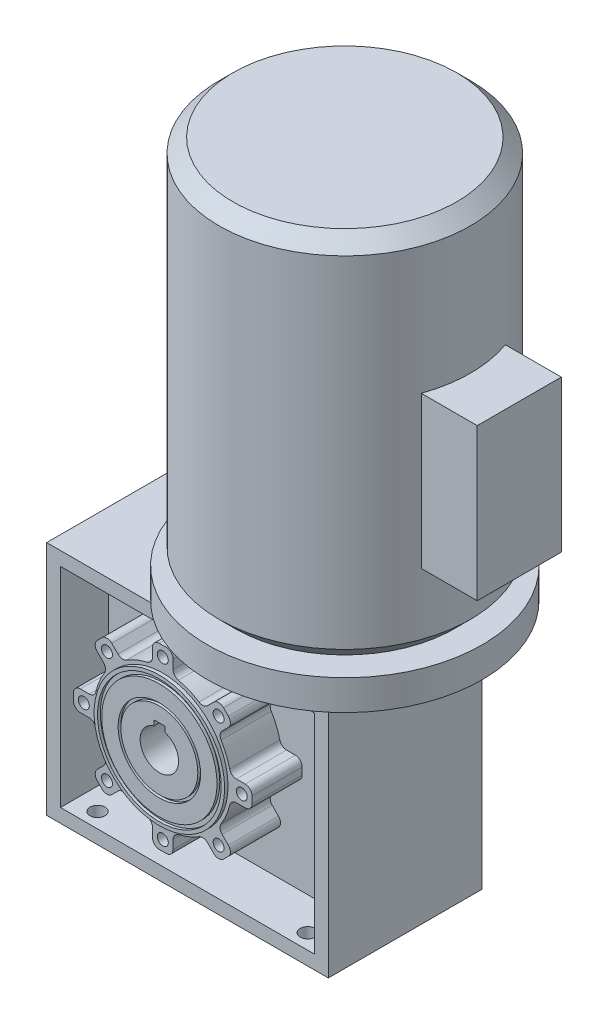
SolidWorks part; units mm, degrees
material "201 Annealed Stainless Steel (SS)"
ref_plane "Front Plane" through (0, 0, 0) normal (0, 0, 1) x (1, 0, 0)
ref_plane "Top Plane" through (0, 0, 0) normal (0, 1, 0) x (1, 0, 0)
ref_plane "Right Plane" through (0, 0, 0) normal (1, 0, 0) x (0, 0, -1)
sketch "Sketch1" plane through (0, 0, 0) normal (0, 0, 1) x (1, 0, 0)
  line L0 (214, -77.2819) -> (214, 49.2287) construction
  line L1 (61, -65.4596) -> (61, 55.7174) construction
  line L2 (125, 99.4164) -> (125, 103.3) construction
  line L3 (125, 103.3) -> (117, 103.3) construction
  line L4 (117, 103.3) -> (117, 99.4164) construction
  line L5 (121, 86) -> (121, 117.4858) construction
  line L8 (35, 0) -> (240, 0)
  line L9 (240, 0) -> (240, 172)
  line L10 (240, 172) -> (35, 172)
  line L11 (35, 172) -> (35, 0)
  circle A1 centre (121, 86) radius 14
  dimension "D1" = 86
  dimension "D2" = 86
  dimension "D6" = 28
  dimension "D3" = 205
  dimension "D4" = 172
  dimension "D5" = 35
  dimension "D7" = 93
  dimension "D8" = 60
  dimension "D9" = 31.3
  dimension "D10" = 8
extrude "Boss-Extrude1" add sketch "Sketch1" against normal blind 112
ref_plane "Plane1" through (0, 0, -56) normal (0, 0, 1) x (1, 0, 0)
sketch "Sketch3" plane through (0, 172, 0) normal (0, 1, 0) x (1, 0, 0)
  circle A1 centre (228, 65) radius 110
sketch "Sketch2" plane through (0, 0, -56) normal (0, 0, 1) x (1, 0, 0)
  line L0 (196, 62.1488) -> (196, 501.4136) construction
  line L1 (275.7058, 210) -> (287.5335, 221.8277)
  line L2 (287.5335, 221.8277) -> (287.5335, 469.9173)
  line L3 (287.5335, 469.9173) -> (277.4507, 480)
  line L4 (277.4507, 480) -> (196, 480)
  line L5 (35, 0) -> (240, 0) construction
  line L6 (275.7058, 210) -> (296, 210)
  line L7 (296, 210) -> (296, 199)
  line L8 (196, 210) -> (275.7058, 210) construction
  line L9 (196, 172) -> (196, 480)
  line L10 (296, 199) -> (237.6683, 199) construction
  line L11 (35, 0) -> (240, 0) construction
  line L12 (237.6683, 188) -> (237.6683, 172)
  line L13 (240, 172) -> (35, 172) construction
  line L14 (237.6683, 172) -> (196, 172)
  line L15 (296, 199) -> (296, 188)
  line L16 (296, 188) -> (237.6683, 188)
  dimension "D1" = 480
  dimension "D2" = 281
  dimension "D3" = 199
  dimension "D4" = 75
  dimension "D5" = 113
  dimension "D6" = 45
  dimension "D7" = 45
  dimension "D8" = 200
  dimension "D9" = 188
revolve "Motor" add sketch "Sketch2" angle 360 about L0
sketch "Sketch4" plane through (0, 0, 0) normal (0, 0, 1) x (1, 0, 0)
  line L8 (230, 10) -> (230, 162)
  line L9 (45, 10) -> (230, 10)
  line L10 (45, 162) -> (45, 10)
  line L11 (230, 162) -> (45, 162)
  line L12 (230, 10) -> (230, 162)
  line L13 (45, 10) -> (230, 10)
  line L14 (45, 162) -> (45, 10)
  line L15 (230, 162) -> (45, 162)
  circle A0 centre (121, 86) radius 50
  circle A1 centre (121, 86) radius 14 construction
  dimension "D2" = 100
  dimension "D1" = 10
extrude "Cut-Extrude1" cut sketch "Sketch4" against normal blind 35
sketch "Sketch5" plane through (0, 0, -112) normal (0, 0, -1) x (-1, 0, 0)
  line L4 (-230, 162) -> (-230, 10)
  line L5 (-45, 162) -> (-230, 162)
  line L6 (-45, 10) -> (-45, 162)
  line L7 (-230, 10) -> (-45, 10)
  line L8 (-230, 162) -> (-230, 10)
  line L9 (-45, 162) -> (-230, 162)
  line L10 (-45, 10) -> (-45, 162)
  line L11 (-230, 10) -> (-45, 10)
  circle A1 centre (-121, 86) radius 50
  circle A2 centre (-121, 86) radius 50
  dimension "D1" = 0
  dimension "D2" = 0
extrude "Cut-Extrude2" cut sketch "Sketch5" against normal blind 46
sketch "Sketch6" plane through (0, 0, 0) normal (0, 0, 1) x (1, 0, 0)
  line L0 (121, 86) -> (121, 219.6781) construction
  line L1 (121, 86) -> (299.9938, 86) construction
  line L2 (113.5, 135.4343) -> (113.5, 151)
  line L3 (113.5, 151) -> (128.5, 151)
  line L4 (128.5, 135.4343) -> (128.5, 151)
  circle A0 centre (121, 143.5) radius 4 construction
  circle A1 centre (121, 28.5) radius 4 construction
  arc A2 (128.5, 135.4343) -> (113.5, 135.4343) centre (121, 86) ccw
  circle A3 centre (121, 86) radius 50 construction
  circle A4 centre (121, 86) radius 57.5 construction
  point P14 (121, 151)
  dimension "D1" = 8
  dimension "D2" = 115
  dimension "D4" = 15
  dimension "D3" = 15
extrude "Boss-Extrude2" add sketch "Sketch6" against normal up to surface (112 mm away) up to face at (135, 86, -112)
ref_axis "Axis1" through (121, 86, -112) along (0, 0, 1)
sketch "Sketch7" plane through (0, 0, 0) normal (0, 0, 1) x (1, 0, 0)
  circle A0 centre (121, 143.5) radius 4 construction
  circle A1 centre (121, 143.5) radius 4
extrude "Cut-Extrude3" cut sketch "Sketch7" against normal through all
fillet "Fillet1" radius 5 8 edges at (128.5, 151, -17.5) (128.5, 135.4343, -17.5) (113.5, 135.4343, -17.5) (113.5, 151, -17.5) (128.5, 135.4343, -89) (128.5, 151, -89) (113.5, 151, -89) (113.5, 135.4343, -89)
pattern_circular "CirPattern1" count 8 over 360 about axis through (121, 86, -112) along (0, 0, 1) of "Boss-Extrude2", "Cut-Extrude3", "Fillet1"
sketch "Sketch8" plane through (0, 0, 0) normal (0, 0, 1) x (1, 0, 0)
  line L4 (88.4302, 129.1764) -> (83.8769, 133.7297)
  line L14 (88.4302, 129.1764) -> (83.8769, 133.7297)
  line L16 (76.8058, 133.7297) -> (73.2703, 130.1942)
  line L18 (76.8058, 133.7297) -> (73.2703, 130.1942)
  line L20 (73.2703, 123.1231) -> (77.8236, 118.5698)
  line L22 (73.2703, 123.1231) -> (77.8236, 118.5698)
  line L76 (67.4393, 93.5) -> (61, 93.5)
  line L78 (67.4393, 93.5) -> (61, 93.5)
  line L80 (56, 88.5) -> (56, 83.5)
  line L82 (56, 88.5) -> (56, 83.5)
  line L84 (61, 78.5) -> (67.4393, 78.5)
  line L86 (61, 78.5) -> (67.4393, 78.5)
  line L88 (77.8236, 53.4302) -> (73.2703, 48.8769)
  line L90 (77.8236, 53.4302) -> (73.2703, 48.8769)
  line L92 (73.2703, 41.8058) -> (76.8058, 38.2703)
  line L94 (73.2703, 41.8058) -> (76.8058, 38.2703)
  line L96 (83.8769, 38.2703) -> (88.4302, 42.8236)
  line L98 (83.8769, 38.2703) -> (88.4302, 42.8236)
  line L100 (113.5, 32.4393) -> (113.5, 26)
  line L101 (113.5, 32.4393) -> (113.5, 26)
  line L102 (118.5, 21) -> (123.5, 21)
  line L103 (118.5, 21) -> (123.5, 21)
  line L104 (128.5, 26) -> (128.5, 32.4393)
  line L105 (128.5, 26) -> (128.5, 32.4393)
  line L106 (153.5698, 42.8236) -> (158.1231, 38.2703)
  line L107 (153.5698, 42.8236) -> (158.1231, 38.2703)
  line L108 (165.1942, 38.2703) -> (168.7297, 41.8058)
  line L109 (165.1942, 38.2703) -> (168.7297, 41.8058)
  line L110 (168.7297, 48.8769) -> (164.1764, 53.4302)
  line L111 (168.7297, 48.8769) -> (164.1764, 53.4302)
  line L112 (174.5607, 78.5) -> (181, 78.5)
  line L113 (174.5607, 78.5) -> (181, 78.5)
  line L114 (186, 83.5) -> (186, 88.5)
  line L115 (186, 83.5) -> (186, 88.5)
  line L116 (181, 93.5) -> (174.5607, 93.5)
  line L117 (181, 93.5) -> (174.5607, 93.5)
  line L118 (164.1764, 118.5698) -> (168.7297, 123.1231)
  line L119 (164.1764, 118.5698) -> (168.7297, 123.1231)
  line L120 (168.7297, 130.1942) -> (165.1942, 133.7297)
  line L121 (168.7297, 130.1942) -> (165.1942, 133.7297)
  line L122 (158.1231, 133.7297) -> (153.5698, 129.1764)
  line L123 (158.1231, 133.7297) -> (153.5698, 129.1764)
  line L124 (128.5, 139.5607) -> (128.5, 146)
  line L125 (128.5, 139.5607) -> (128.5, 146)
  line L126 (123.5, 151) -> (118.5, 151)
  line L127 (123.5, 151) -> (118.5, 151)
  line L128 (113.5, 146) -> (113.5, 139.5607)
  line L129 (113.5, 146) -> (113.5, 139.5607)
  circle A0 centre (161.6586, 45.3414) radius 4 construction
  circle A1 centre (121, 28.5) radius 4 construction
  circle A2 centre (80.3414, 45.3414) radius 4 construction
  circle A3 centre (63.5, 86) radius 4 construction
  circle A4 centre (178.5, 86) radius 4 construction
  circle A5 centre (161.6586, 126.6586) radius 4 construction
  circle A6 centre (121, 86) radius 14 construction
  circle A7 centre (80.3414, 126.6586) radius 4 construction
  circle A24 centre (121, 143.5) radius 4 construction
  circle A25 centre (161.6586, 45.3414) radius 4
  circle A26 centre (121, 28.5) radius 4
  circle A27 centre (80.3414, 45.3414) radius 4
  circle A28 centre (63.5, 86) radius 4
  circle A29 centre (178.5, 86) radius 4
  circle A30 centre (161.6586, 126.6586) radius 4
  circle A31 centre (121, 86) radius 14
  circle A32 centre (80.3414, 126.6586) radius 4
  circle A33 centre (121, 143.5) radius 4
  arc A70 (168.7297, 123.1231) -> (168.7297, 130.1942) centre (165.1942, 126.6586) ccw
  arc A72 (168.7297, 123.1231) -> (168.7297, 130.1942) centre (165.1942, 126.6586) ccw
  arc A74 (165.1942, 133.7297) -> (158.1231, 133.7297) centre (161.6586, 130.1942) ccw
  arc A78 (165.1942, 133.7297) -> (158.1231, 133.7297) centre (161.6586, 130.1942) ccw
  arc A82 (147.3948, 128.4654) -> (153.5698, 129.1764) centre (150.0343, 132.712) ccw
  arc A86 (147.3948, 128.4654) -> (153.5698, 129.1764) centre (150.0343, 132.712) ccw
  arc A90 (147.3948, 128.4654) -> (132.3636, 134.6916) centre (121, 86) ccw
  arc A94 (147.3948, 128.4654) -> (132.3636, 134.6916) centre (121, 86) ccw
  arc A98 (128.5, 139.5607) -> (132.3636, 134.6916) centre (133.5, 139.5607) ccw
  arc A102 (128.5, 139.5607) -> (132.3636, 134.6916) centre (133.5, 139.5607) ccw
  arc A106 (128.5, 146) -> (123.5, 151) centre (123.5, 146) ccw
  arc A110 (128.5, 146) -> (123.5, 151) centre (123.5, 146) ccw
  arc A114 (118.5, 151) -> (113.5, 146) centre (118.5, 146) ccw
  arc A118 (118.5, 151) -> (113.5, 146) centre (118.5, 146) ccw
  arc A122 (109.6364, 134.6916) -> (113.5, 139.5607) centre (108.5, 139.5607) ccw
  arc A126 (109.6364, 134.6916) -> (113.5, 139.5607) centre (108.5, 139.5607) ccw
  arc A130 (109.6364, 134.6916) -> (94.6052, 128.4654) centre (121, 86) ccw
  arc A134 (109.6364, 134.6916) -> (94.6052, 128.4654) centre (121, 86) ccw
  arc A138 (88.4302, 129.1764) -> (94.6052, 128.4654) centre (91.9657, 132.712) ccw
  arc A142 (88.4302, 129.1764) -> (94.6052, 128.4654) centre (91.9657, 132.712) ccw
  arc A146 (83.8769, 133.7297) -> (76.8058, 133.7297) centre (80.3414, 130.1942) ccw
  arc A148 (83.8769, 133.7297) -> (76.8058, 133.7297) centre (80.3414, 130.1942) ccw
  arc A150 (73.2703, 130.1942) -> (73.2703, 123.1231) centre (76.8058, 126.6586) ccw
  arc A152 (73.2703, 130.1942) -> (73.2703, 123.1231) centre (76.8058, 126.6586) ccw
  arc A154 (78.5346, 112.3948) -> (77.8236, 118.5698) centre (74.288, 115.0343) ccw
  arc A156 (78.5346, 112.3948) -> (77.8236, 118.5698) centre (74.288, 115.0343) ccw
  arc A158 (78.5346, 112.3948) -> (72.3084, 97.3636) centre (121, 86) ccw
  arc A160 (78.5346, 112.3948) -> (72.3084, 97.3636) centre (121, 86) ccw
  arc A162 (67.4393, 93.5) -> (72.3084, 97.3636) centre (67.4393, 98.5) ccw
  arc A164 (67.4393, 93.5) -> (72.3084, 97.3636) centre (67.4393, 98.5) ccw
  arc A166 (61, 93.5) -> (56, 88.5) centre (61, 88.5) ccw
  arc A168 (61, 93.5) -> (56, 88.5) centre (61, 88.5) ccw
  arc A170 (56, 83.5) -> (61, 78.5) centre (61, 83.5) ccw
  arc A172 (56, 83.5) -> (61, 78.5) centre (61, 83.5) ccw
  arc A174 (72.3084, 74.6364) -> (67.4393, 78.5) centre (67.4393, 73.5) ccw
  arc A176 (72.3084, 74.6364) -> (67.4393, 78.5) centre (67.4393, 73.5) ccw
  arc A178 (72.3084, 74.6364) -> (78.5346, 59.6052) centre (121, 86) ccw
  arc A180 (72.3084, 74.6364) -> (78.5346, 59.6052) centre (121, 86) ccw
  arc A182 (77.8236, 53.4302) -> (78.5346, 59.6052) centre (74.288, 56.9657) ccw
  arc A184 (77.8236, 53.4302) -> (78.5346, 59.6052) centre (74.288, 56.9657) ccw
  arc A186 (73.2703, 48.8769) -> (73.2703, 41.8058) centre (76.8058, 45.3414) ccw
  arc A187 (73.2703, 48.8769) -> (73.2703, 41.8058) centre (76.8058, 45.3414) ccw
  arc A188 (76.8058, 38.2703) -> (83.8769, 38.2703) centre (80.3414, 41.8058) ccw
  arc A189 (76.8058, 38.2703) -> (83.8769, 38.2703) centre (80.3414, 41.8058) ccw
  arc A190 (94.6052, 43.5346) -> (88.4302, 42.8236) centre (91.9657, 39.288) ccw
  arc A191 (94.6052, 43.5346) -> (88.4302, 42.8236) centre (91.9657, 39.288) ccw
  arc A192 (94.6052, 43.5346) -> (109.6364, 37.3084) centre (121, 86) ccw
  arc A193 (94.6052, 43.5346) -> (109.6364, 37.3084) centre (121, 86) ccw
  arc A194 (113.5, 32.4393) -> (109.6364, 37.3084) centre (108.5, 32.4393) ccw
  arc A195 (113.5, 32.4393) -> (109.6364, 37.3084) centre (108.5, 32.4393) ccw
  arc A196 (113.5, 26) -> (118.5, 21) centre (118.5, 26) ccw
  arc A197 (113.5, 26) -> (118.5, 21) centre (118.5, 26) ccw
  arc A198 (123.5, 21) -> (128.5, 26) centre (123.5, 26) ccw
  arc A199 (123.5, 21) -> (128.5, 26) centre (123.5, 26) ccw
  arc A200 (132.3636, 37.3084) -> (128.5, 32.4393) centre (133.5, 32.4393) ccw
  arc A201 (132.3636, 37.3084) -> (128.5, 32.4393) centre (133.5, 32.4393) ccw
  arc A202 (132.3636, 37.3084) -> (147.3948, 43.5346) centre (121, 86) ccw
  arc A203 (132.3636, 37.3084) -> (147.3948, 43.5346) centre (121, 86) ccw
  arc A204 (153.5698, 42.8236) -> (147.3948, 43.5346) centre (150.0343, 39.288) ccw
  arc A205 (153.5698, 42.8236) -> (147.3948, 43.5346) centre (150.0343, 39.288) ccw
  arc A206 (158.1231, 38.2703) -> (165.1942, 38.2703) centre (161.6586, 41.8058) ccw
  arc A207 (158.1231, 38.2703) -> (165.1942, 38.2703) centre (161.6586, 41.8058) ccw
  arc A208 (168.7297, 41.8058) -> (168.7297, 48.8769) centre (165.1942, 45.3414) ccw
  arc A209 (168.7297, 41.8058) -> (168.7297, 48.8769) centre (165.1942, 45.3414) ccw
  arc A210 (163.4654, 59.6052) -> (164.1764, 53.4302) centre (167.712, 56.9657) ccw
  arc A211 (163.4654, 59.6052) -> (164.1764, 53.4302) centre (167.712, 56.9657) ccw
  arc A212 (163.4654, 59.6052) -> (169.6916, 74.6364) centre (121, 86) ccw
  arc A213 (163.4654, 59.6052) -> (169.6916, 74.6364) centre (121, 86) ccw
  arc A214 (174.5607, 78.5) -> (169.6916, 74.6364) centre (174.5607, 73.5) ccw
  arc A215 (174.5607, 78.5) -> (169.6916, 74.6364) centre (174.5607, 73.5) ccw
  arc A216 (181, 78.5) -> (186, 83.5) centre (181, 83.5) ccw
  arc A217 (181, 78.5) -> (186, 83.5) centre (181, 83.5) ccw
  arc A218 (186, 88.5) -> (181, 93.5) centre (181, 88.5) ccw
  arc A219 (186, 88.5) -> (181, 93.5) centre (181, 88.5) ccw
  arc A220 (169.6916, 97.3636) -> (174.5607, 93.5) centre (174.5607, 98.5) ccw
  arc A221 (169.6916, 97.3636) -> (174.5607, 93.5) centre (174.5607, 98.5) ccw
  arc A222 (169.6916, 97.3636) -> (163.4654, 112.3948) centre (121, 86) ccw
  arc A223 (169.6916, 97.3636) -> (163.4654, 112.3948) centre (121, 86) ccw
  arc A224 (164.1764, 118.5698) -> (163.4654, 112.3948) centre (167.712, 115.0343) ccw
  arc A225 (164.1764, 118.5698) -> (163.4654, 112.3948) centre (167.712, 115.0343) ccw
  dimension "D1" = 0
extrude "Boss-Extrude one side" add sketch "Sketch8" along normal blind 1.5
sketch "Sketch9" plane through (0, 0, 1.5) normal (0, 0, 1) x (1, 0, 0)
  circle A0 centre (121, 86) radius 47.5
  circle A1 centre (121, 86) radius 14 construction
  circle A2 centre (121, 86) radius 14
  dimension "D1" = 95
extrude "Boss-Extrude5" add sketch "Sketch9" along normal blind 2.5
sketch "Sketch10" plane through (0, 0, 4) normal (0, 0, 1) x (1, 0, 0)
  circle A0 centre (121, 86) radius 45
  circle A1 centre (121, 86) radius 42
  dimension "D1" = 90
  dimension "D2" = 84
extrude "Cut-Extrude4" cut sketch "Sketch10" against normal blind 2
sketch "Sketch11" plane through (0, 0, 4) normal (0, 0, 1) x (1, 0, 0)
  circle A0 centre (121, 86) radius 30
  circle A1 centre (121, 86) radius 14 construction
  circle A2 centre (121, 86) radius 28
  dimension "D1" = 60
  dimension "D2" = 2
extrude "Cut-Extrude5" cut sketch "Sketch11" against normal up to surface (2 mm away) up to face at (163, 86, 2)
sketch "Sketch12" plane through (240, 0, 0) normal (1, 0, 0) x (0, 0, -1)
  line L0 (56, 158.4) -> (56, -158.4) construction
  line L1 (25.4071, 377.0348) -> (86.5929, 377.0348)
  line L2 (25.4071, 377.0348) -> (25.4071, 266.6375)
  line L3 (25.4071, 266.6375) -> (86.5929, 266.6375)
  line L4 (86.5929, 377.0348) -> (86.5929, 266.6375)
  line L5 (25.4071, 377.0348) -> (86.5929, 266.6375) construction
  line L6 (25.4071, 266.6375) -> (86.5929, 377.0348) construction
  point P0 (56, 321.8362)
extrude "Boss-Extrude6" add sketch "Sketch12" along normal offset from surface (83 mm away) 288 up to face at (35, 86, -56)
mirror "Mirror1" about plane through (0, 0, -56) normal (0, 0, 1) of "Cut-Extrude5", "Cut-Extrude4", "Boss-Extrude5", "Boss-Extrude one side"
sketch "Sketch14" plane through (0, 0, 0) normal (0, -1, 0) x (1, 0, 0)
  line L0 (240, -56) -> (306.3943, -56) construction
  line L1 (240, -112) -> (240, 0) construction
  line L2 (137.5, -60.53) -> (137.5, 72.4647) construction
  circle A0 centre (214, -11) radius 5.5
  circle A1 centre (214, -101) radius 5.5
  circle A2 centre (61, -101) radius 5.5
  circle A3 centre (61, -11) radius 5.5
  dimension "D1" = 90
  dimension "D2" = 11
  dimension "D3" = 153
extrude "Cut-Extrude6" cut sketch "Sketch14" against normal blind 15
sketch "Sketch15" plane through (0, 0, 4) normal (0, 0, 1) x (1, 0, 0)
  line L0 (125, 99.4164) -> (125, 103.3) construction
  line L1 (125, 103.3) -> (117, 103.3) construction
  line L2 (117, 103.3) -> (117, 99.4164) construction
  line L3 (125, 99.4164) -> (125, 103.3)
  line L4 (125, 103.3) -> (117, 103.3)
  line L5 (117, 103.3) -> (117, 99.4164)
  circle A0 centre (121, 86) radius 14 construction
  arc A1 (125, 99.4164) -> (117, 99.4164) centre (121, 86) ccw
extrude "Cut-Extrude7" cut sketch "Sketch15" against normal through all
ref_plane "Centre Plane" through (137.5, 0, 0) normal (1, 0, 0) x (0, 0, -1)
